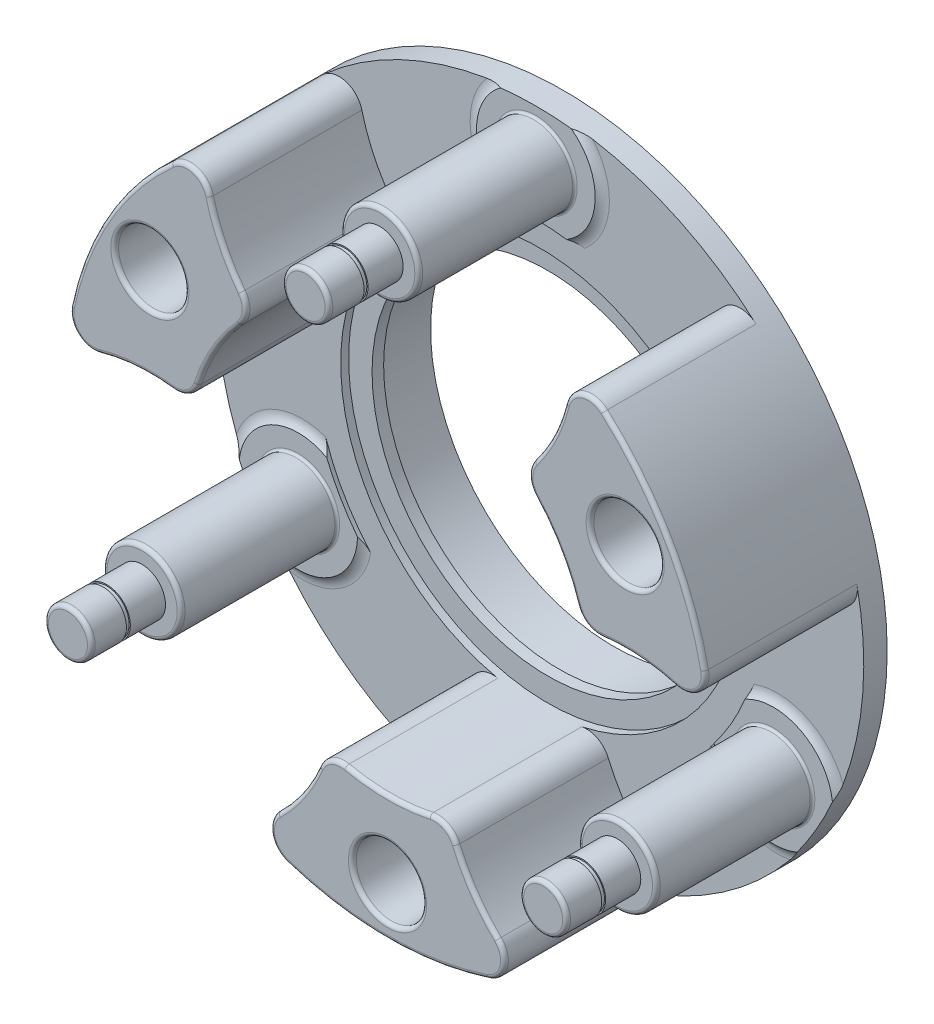
SolidWorks part; units mm, degrees
material "7075-T6 (SN)"
ref_plane "Front Plane" through (0, 0, 0) normal (0, 0, 1) x (1, 0, 0)
ref_plane "Top Plane" through (0, 0, 0) normal (0, 1, 0) x (1, 0, 0)
ref_plane "Right Plane" through (0, 0, 0) normal (1, 0, 0) x (0, 0, -1)
sketch "Sketch1" plane through (0, 0, 0) normal (0, 0, 1) x (1, 0, 0)
  line L0 (0, 0) -> (0, 35.1474) construction
  line L1 (0, 0) -> (-30.4385, 17.5737) construction
  circle A0 centre (0, 0) radius 5 construction
  circle A1 centre (0, 35.1474) radius 3
  circle A2 centre (0, 0) radius 25.5
  circle A3 centre (0, 0) radius 41.5
  circle A4 centre (30.4385, -17.5737) radius 3
  circle A5 centre (-30.4385, -17.5737) radius 3
  circle A10 centre (-30.4385, 17.5737) radius 2.1
  circle A11 centre (30.4385, 17.5737) radius 2.1
  circle A12 centre (0, -35.1474) radius 2.1
  point P13 (0, 0)
  point P20 (0, 0)
  point P21 (0, 0)
  dimension "D1" = 10
  dimension "D3" = 6
  dimension "D4" = 51
  dimension "D5" = 83
  dimension "D9" = 4.2
  dimension "D2" = 35.1474
  dimension "D7" = 35.1474
  dimension "D8" = 60
  dimension "D6" = 3
  dimension "D10" = 3
extrude "Boss-Extrude1" add sketch "Sketch1" along normal blind 3
sketch "Sketch3" plane through (0, 0, 3) normal (0, 0, 1) x (1, 0, 0)
  line L0 (0, 0) -> (0, 35.1474) construction
  line L1 (0, 0) -> (-30.4385, 17.5737) construction
  circle A4 centre (0, 35.1474) radius 23.5
  circle A14 centre (-30.4385, 17.5737) radius 4.5
  circle A15 centre (0, 0) radius 41.5
  circle A18 centre (-30.4385, 17.5737) radius 3
  circle A21 centre (0, 0) radius 5.0736 construction
  circle A22 centre (30.4385, 17.5737) radius 3
  circle A23 centre (30.4385, 17.5737) radius 4.5
  circle A24 centre (30.4385, -17.5737) radius 23.5
  circle A25 centre (0, -35.1474) radius 3
  circle A26 centre (0, -35.1474) radius 4.5
  circle A27 centre (-30.4385, -17.5737) radius 23.5
  point P18 (0, 0)
  point P22 (0, 0)
  dimension "D2" = 35.1474
  dimension "D6" = 35.1474
  dimension "D1" = 47
  dimension "D4" = 9
  dimension "D5" = 6
  dimension "D7" = 3
  dimension "D3" = 60
extrude "Boss-Extrude2" add sketch "Sketch3" along normal blind 19.5
sketch "Sketch9" plane through (0, 0, 3) normal (0, 0, 1) x (1, 0, 0)
  circle A0 centre (0, 35.1474) radius 3 construction
  circle A1 centre (0, 35.1474) radius 3
  arc A2 (3.9457, 28.6519) -> (4.5265, 41.2524) centre (0, 35.1474) ccw
  arc A3 (23.4816, 34.2179) -> (-23.4816, 34.2179) centre (0, 0) ccw construction
  arc A4 (3.9457, 28.6519) -> (-3.9457, 28.6519) centre (0, 0) ccw
  arc A5 (4.5265, 41.2524) -> (-4.5265, 41.2524) centre (0, 0) ccw
  arc A7 (-4.5265, 41.2524) -> (-3.9457, 28.6519) centre (0, 35.1474) ccw
extrude "Boss-Extrude3" add sketch "Sketch9" along normal blind 0.5
fillet "Fillet4" radius 2 6 edges at (-7.5919, 34.7975, 3) (-4.5265, 41.2524, 3.25) (-3.9457, 28.6519, 3.25) (7.5919, 34.7975, 3) (3.9457, 28.6519, 3.25) (4.5265, 41.2524, 3.25)
fillet "Fillet5" radius 3 12 edges at (-23.4816, 34.2179, 12.75) (-17.0432, 18.9678, 12.75) (17.0432, 18.9678, 12.75) (23.4816, 34.2179, 12.75) (24.9482, 5.276, 12.75) (41.3744, 3.2267, 12.75) (7.905, -24.2438, 12.75) (17.8928, -37.4446, 12.75) (-7.905, -24.2438, 12.75) (-17.8928, -37.4446, 12.75) (-24.9482, 5.276, 12.75) (-41.3744, 3.2267, 12.75)
sketch "Sketch10" plane through (0, 0, 0) normal (0, 0, -1) x (-1, 0, 0)
  circle A0 centre (-30.4385, 17.5737) radius 7.5
  arc A1 (-24.2416, 29.0365) -> (-21.7869, 22.8865) centre (0, 35.1474) ccw
  arc A2 (-24.2416, 29.0365) -> (-26.6973, 29.7868) centre (-25.6961, 28.6698) ccw
  arc A3 (-26.6973, 29.7868) -> (-39.1454, 8.2242) centre (0, 0) ccw
  arc A4 (-39.1454, 8.2242) -> (-37.2677, 6.4729) centre (-37.6774, 7.9158) ccw
  arc A5 (-30.7145, 7.4222) -> (-37.2677, 6.4729) centre (-30.4385, -17.5763) ccw
  arc A6 (-30.7145, 7.4222) -> (-29.2905, 8.5039) centre (-30.731, 8.9221) ccw
  arc A7 (-22.0116, 21.1125) -> (-29.2905, 8.5039) centre (0, 0) ccw
  arc A8 (-22.0116, 21.1125) -> (-21.7869, 22.8865) centre (-23.0941, 22.1509) ccw
  dimension "D1" = 35.1474
extrude "Cut-Extrude5" cut sketch "Sketch10" against normal offset from surface (17.5 mm away) 5 contours A7 A0 A3 A4 A5 A6 | A7 A8 A1 A2 A3 A0 up to face at (27.4512, 15.849, 22.5)
sketch "Sketch11" plane through (0, 0, 0) normal (0, 1, 0) x (1, 0, 0)
  line L5 (-25.5, 6.5163) -> (-23.5, 6.5163)
  line L6 (0, 0) -> (0, 22.9582) construction
  line L9 (-25.5, -1.9837) -> (-22.5, -1.9837)
  line L12 (-23.5, -0.5) -> (-22.5, -0.5)
  line L13 (-22.5, -0.5) -> (-22.5, -1.9837)
  line L14 (-23.5, 6.5163) -> (-23.5, -0.5)
  line L15 (41.5, 0) -> (-41.5, 0) construction
  line L16 (-25.5, 6.5163) -> (-25.5, -1.9837)
  dimension "D2" = 0.5
  dimension "D1" = 2
  dimension "D6" = 23.5
  dimension "D7" = 1
revolve "Revolve1" add sketch "Sketch11" angle 360 about L6
sketch "Sketch12" plane through (0, 0, 3.5) normal (0, 0, 1) x (1, 0, 0)
  line L0 (0, 35.1474) -> (0, 0) construction
  circle A2 centre (0, 35.1474) radius 5
  dimension "D1" = 10
  dimension "D2" = 35.1474
extrude "Cut-Extrude6" cut sketch "Sketch12" against normal blind 2
sketch "Sketch13" plane through (0, 0, 3) normal (0, 0, 1) x (1, 0, 0)
  circle A0 centre (-30.4385, 17.5737) radius 2.1 construction
  circle A1 centre (-30.4385, 17.5737) radius 4.5
  circle A2 centre (-30.4385, 17.5737) radius 4.5
  circle A3 centre (-30.4385, 17.5737) radius 2.1
  dimension "D1" = 0
extrude "Boss-Extrude5" add sketch "Sketch13" along normal offset from surface (9.5 mm away) 10 up to face at (-27.4512, 15.849, 22.5)
fillet "Fillet7" radius 0.5 27 edges at (-25.9385, 17.5737, 22.5) (32.2183, 5.8588, 22.5) (39.7232, 5.7248, 22.5) (35.9401, 20.75, 22.5) (24.8195, 31.5389, 22.5) (21.183, 24.9724, 22.5) (18.1208, 19.0071, 22.5) (22.0836, 12.75, 22.5) (25.5211, 6.1895, 22.5) (4.5, -35.1474, 22.5) (34.9385, 17.5737, 22.5) (-14.9037, -37.2637, 22.5) (0, -41.5, 22.5) (14.9037, -37.2637, 22.5) (11.0353, -30.8313, 22.5) (7.4003, -25.1966, 22.5) (-7.4003, -25.1966, 22.5) (-11.0353, -30.8313, 22.5) (0, -25.5, 22.5) (-39.7232, 5.7248, 22.5) (-25.5211, 6.1895, 22.5) (-32.2183, 5.8588, 22.5) (-18.1208, 19.0071, 22.5) (-22.0836, 12.75, 22.5) (-35.9401, 20.75, 22.5) (-21.183, 24.9724, 22.5) (-24.8195, 31.5389, 22.5)
pattern_circular "CirPattern2" count 3 over 360 about axis through (0, 0, 0) along (0, 0, 1) of "Boss-Extrude3", "Fillet4", "Cut-Extrude5", "Cut-Extrude6"
sketch "Sketch15" plane through (0, 0, 3) normal (0, 0, 1) x (1, 0, 0)
  line L0 (0, 0) -> (30.4385, 17.5737) construction
  line L1 (0, 0) -> (0, -35.1474) construction
  circle A0 centre (30.4385, 17.5737) radius 2.1
  circle A1 centre (30.4385, 17.5737) radius 4.5
  circle A2 centre (0, -35.1474) radius 2.1
  circle A3 centre (0, -35.1474) radius 4.5
extrude "Boss-Extrude8" add sketch "Sketch15" along normal blind 11.4
chamfer "Chamfer2" distance 0.5 angle 45 3 edges at (-25.9385, 17.5737, 12.5) (4.5, -35.1474, 14.4) (34.9385, 17.5737, 14.4)
fillet "Fillet8" radius 0.3 1 edges at (23.5, 0, 0.5)
sketch "Sketch18" plane through (0, 0, 1.5) normal (0, 0, 1) x (1, 0, 0)
  circle A0 centre (0, 35.1474) radius 3
extrude "Boss-Extrude10" add sketch "Sketch18" against normal blind 3
pattern_circular "CirPattern4" count 3 over 360 about axis through (0, 0, 0) along (0, 0, 1) of "Boss-Extrude10"
sketch "Sketch19" plane through (0, 0, 1.5) normal (0, 0, 1) x (1, 0, 0)
  circle A0 centre (0, 35.1474) radius 5
extrude "Boss-Extrude11" add sketch "Sketch19" along normal blind 22
pattern_circular "CirPattern6" count 3 over 360 about axis through (0, 0, 0) along (0, 0, 1) of "Boss-Extrude11"
fillet "Fillet11" radius 0.5 3 edges at (27.9385, -21.9038, 23.5) (-32.9385, -13.2436, 23.5) (5, 35.1474, 23.5)
fillet "Fillet13" radius 0.3 3 edges at (27.9385, -21.9038, 3.5) (-32.9385, -13.2436, 3.5) (5, 35.1474, 3.5)
sketch "Sketch20" plane through (0, 0, -1.5) normal (0, 0, -1) x (-1, 0, 0)
  circle A1 centre (0, 35.1474) radius 3
  circle A2 centre (0, 35.1474) radius 3
  dimension "D1" = 0
extrude "Cut-Extrude7" cut sketch "Sketch20" against normal up to surface (1.5 mm away) up to face at (-9.271, -33.8424, 0)
pattern_circular "CirPattern8" count 3 over 360 of "Cut-Extrude7"
sketch "Sketch21" plane through (0, 0, 23.5) normal (0, 0, 1) x (1, 0, 0)
  circle A0 centre (0, 35.1474) radius 3
  dimension "D1" = 6
extrude "Boss-Extrude12" add sketch "Sketch21" along normal blind 9.5
pattern_circular "CirPattern9" count 3 over 360 about axis through (0, 0, 0) along (0, 0, 1) of "Boss-Extrude12"
fillet "Fillet14" radius 0.5 3 edges at (-31.9385, -14.9756, 33) (28.9385, -20.1718, 33) (3, 35.1474, 33)
ref_plane "Plane1" through (0, 0, 28) normal (0, 0, 1) x (1, 0, 0)
sketch "Sketch22" plane through (0, 0, 28) normal (0, 0, 1) x (1, 0, 0)
  circle A0 centre (0, 35.1474) radius 2.85
  circle A1 centre (0, 35.1474) radius 3
  dimension "D1" = 5.7
  dimension "D2" = 6
extrude "Cut-Extrude8" cut sketch "Sketch22" along normal blind 0.5
pattern_circular "CirPattern10" count 3 over 360 about axis through (0, 0, 0) along (0, 0, 1) of "Cut-Extrude8"
